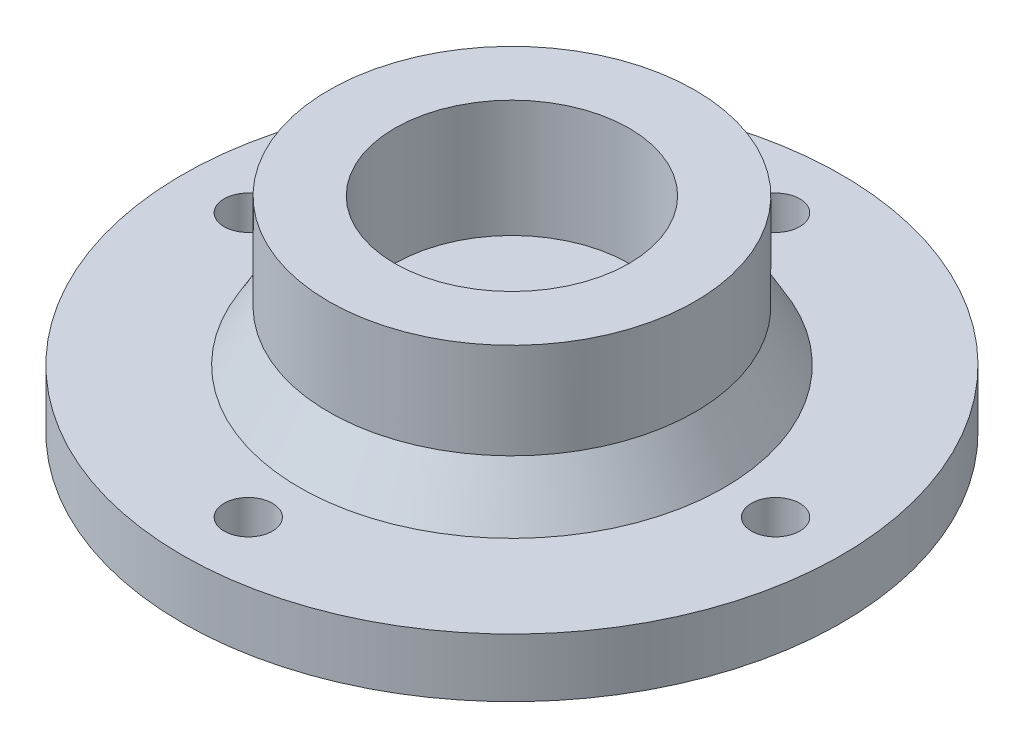
SolidWorks part; units mm, degrees
ref_plane "前视基准面" through (0, 0, 0) normal (0, 0, 1) x (1, 0, 0)
ref_plane "上视基准面" through (0, 0, 0) normal (0, 1, 0) x (1, 0, 0)
ref_plane "右视基准面" through (0, 0, 0) normal (1, 0, 0) x (0, 0, -1)
other "Configuration Table"
sketch "草图1" plane through (0, 0, 0) normal (0, 1, 0) x (1, 0, 0)
  line L0 (0, 0) -> (-18, 0) construction
  line L1 (0, 0) -> (18, 0) construction
  line L2 (0, 0) -> (0, 18) construction
  line L3 (0, 0) -> (0, -18) construction
  circle A0 centre (0, 0) radius 22.5
  circle A1 centre (-18, 0) radius 1.65
  circle A2 centre (18, 0) radius 1.65
  circle A3 centre (0, 18) radius 1.65
  circle A7 centre (0, -18) radius 1.65
  dimension "D1" = 45
  dimension "D2" = 3.3
  dimension "D3" = 18
  dimension "D4" = 18
extrude "凸台-拉伸1" add sketch "草图1" along normal blind 4
sketch "草图2" plane through (0, 4, 0) normal (0, 1, 0) x (1, 0, 0)
  circle A0 centre (0, 0) radius 8
  circle A1 centre (0, 0) radius 12.5
  dimension "D1" = 16
  dimension "D2" = 25
extrude "凸台-拉伸2" add sketch "草图2" along normal blind 10
sketch "草图3" plane through (0, 0, 0) normal (0, -1, 0) x (1, 0, 0)
  circle A0 centre (0, 0) radius 4
  circle A1 centre (0, 0) radius 1.6
  dimension "D1" = 8
  dimension "D2" = 3.2
extrude "切除-拉伸1" cut sketch "草图3" against normal blind 3 contours A0 A1 | A0 region at (-3.8869, 0, 0)
sketch "草图4" plane through (0, 4, 0) normal (0, 1, 0) x (1, 0, 0)
  circle A0 centre (0, 0) radius 8
  dimension "D1" = 16
extrude "凸台-拉伸3" add sketch "草图4" along normal blind 2
extrude "切除-拉伸2" cut sketch "草图3<3>" against normal blind 10 contours A1 region at (0, 0, 0)
sketch "草图3<3>" plane through (0, 0, 0) normal (0, -1, 0) x (1, 0, 0) same geometry as "草图3"
chamfer "倒角1" distance 2 angle 60 1 edges at (0, 4, 12.5) first distance on face at (0, 4, 12.5)
